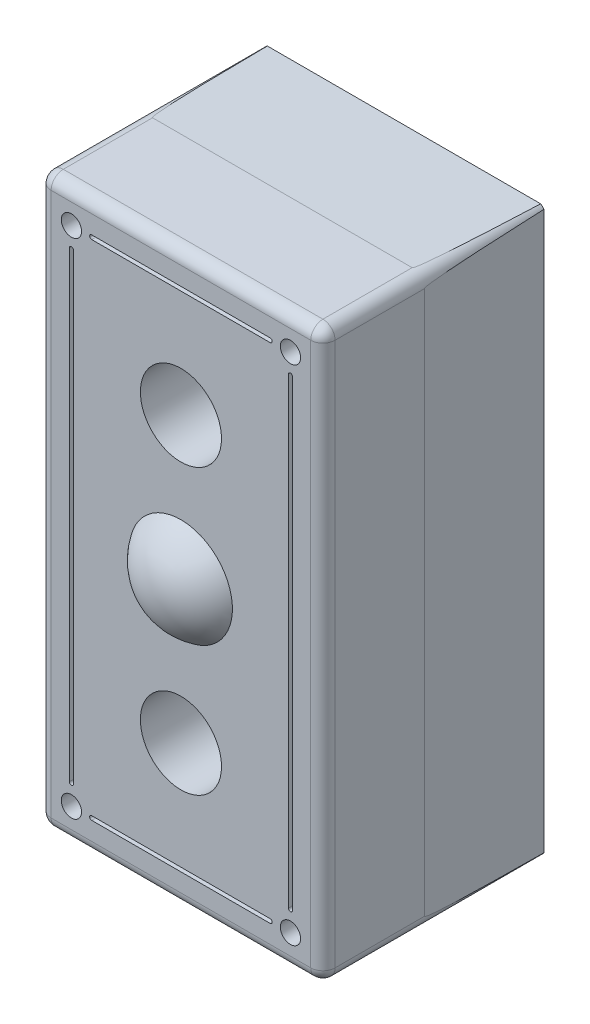
SolidWorks part; units mm, degrees
ref_plane "Front Plane" through (0, 0, 0) normal (0, 0, 1) x (1, 0, 0)
ref_plane "Top Plane" through (0, 0, 0) normal (0, 1, 0) x (1, 0, 0)
ref_plane "Right Plane" through (0, 0, 0) normal (1, 0, 0) x (0, 0, -1)
sketch "Sketch1" plane through (0, 0, 0) normal (0, 0, 1) x (1, 0, 0)
  line L1 (-35, 70) -> (35, 70)
  line L2 (-35, 70) -> (-35, -70)
  line L3 (-35, -70) -> (35, -70)
  line L4 (35, 70) -> (35, -70)
  line L5 (-35, 70) -> (35, -70) construction
  line L6 (-35, -70) -> (35, 70) construction
  point P0 (0, 0)
  dimension "D1" = 70
  dimension "D2" = 140
extrude "Boss-Extrude1" add sketch "Sketch1" against normal blind 30 draft 1
sketch "Sketch2" plane through (0, 0, 0) normal (0, 0, 1) x (1, 0, 0)
  line L4 (35, -70) -> (35, 70)
  line L5 (35, 70) -> (-35, 70)
  line L6 (-35, 70) -> (-35, -70)
  line L7 (-35, -70) -> (35, -70)
  line L8 (35, -70) -> (35, 70)
  line L9 (35, 70) -> (-35, 70)
  line L10 (-35, 70) -> (-35, -70)
  line L11 (-35, -70) -> (35, -70)
  dimension "D1" = 0
extrude "Boss-Extrude2" add sketch "Sketch2" along normal blind 25
sketch "Sketch3" plane through (0, 0, 25) normal (0, 0, 1) x (1, 0, 0)
  line L0 (35, -70) -> (35, 70) construction
  line L1 (35, 70) -> (-35, 70) construction
  circle A0 centre (27, 62) radius 2.5
  dimension "D1" = 8
  dimension "D3" = 5
  dimension "D2" = 8
extrude "Cut-Extrude1" cut sketch "Sketch3" against normal blind 25
mirror "Mirror1" about plane through (0, 0, 0) normal (1, 0, 0) of "Cut-Extrude1"
mirror "Mirror2" about plane through (0, 0, 0) normal (0, 1, 0) of "Mirror1", "Cut-Extrude1"
sketch "Sketch4" plane through (0, 0, 25) normal (0, 0, 1) x (1, 0, 0)
  line L0 (-35, -70) -> (35, -70) construction
  line L1 (35, 70) -> (-35, 70) construction
  circle A0 centre (0, -35) radius 10
  circle A1 centre (0, 35) radius 10
  point P4 (0, 0)
  point P6 (0, 0)
  dimension "D1" = 35
  dimension "D2" = 35
  dimension "D3" = 20
extrude "Cut-Extrude2" cut sketch "Sketch4" against normal blind 25
sketch "Sketch5" plane through (0, 0, 0) normal (0, 1, 0) x (1, 0, 0)
  line L0 (35, -25) -> (-35, -25) construction
  line L1 (0, -25) -> (0, -32) construction
  line L2 (0, -25) -> (0, -32)
  line L3 (12.6886, -25) -> (0, -25)
  arc A0 (12.6886, -25) -> (0, -32) centre (0, -17) cw
  dimension "D1" = 15
  dimension "D2" = 8
revolve "Revolve2" add sketch "Sketch5" angle 360 about L1
fillet "Fillet1" radius 3 8 edges at (-35, 0, 25) (35, 0, 25) (0, -70, 25) (0, 70, 25) (-35, -70, 12.5) (35, -70, 12.5) (-35, 70, 12.5) (35, 70, 12.5)
sketch "Sketch6" plane through (0, 0, 25) normal (0, 0, 1) x (1, 0, 0)
  line L0 (-22, 62) -> (22, 62) construction
  line L1 (-22, 62.5) -> (22, 62.5)
  line L2 (-22, 61.5) -> (22, 61.5)
  line L3 (-32, 70) -> (32, 70) construction
  line L4 (0, 0) -> (24.2245, 0) construction
  line L5 (-22, -62) -> (22, -62) construction
  line L6 (-22, -62.5) -> (22, -62.5)
  line L7 (-22, -61.5) -> (22, -61.5)
  line L8 (27, 57) -> (27, -57) construction
  line L9 (27.5, 57) -> (27.5, -57)
  line L10 (26.5, 57) -> (26.5, -57)
  line L11 (35, 67) -> (35, -67) construction
  line L12 (0, 0) -> (0, 18.2615) construction
  line L13 (-27, 57) -> (-27, -57) construction
  line L14 (-27.5, 57) -> (-27.5, -57)
  line L15 (-26.5, 57) -> (-26.5, -57)
  arc A0 (-22, 62.5) -> (-22, 61.5) centre (-22, 62) ccw
  arc A1 (22, 61.5) -> (22, 62.5) centre (22, 62) ccw
  circle A2 centre (27, 62) radius 2.5 construction
  circle A3 centre (-27, 62) radius 2.5 construction
  arc A4 (-22, -62.5) -> (-22, -61.5) centre (-22, -62) cw
  arc A5 (22, -61.5) -> (22, -62.5) centre (22, -62) cw
  arc A6 (27.5, 57) -> (26.5, 57) centre (27, 57) ccw
  arc A7 (26.5, -57) -> (27.5, -57) centre (27, -57) ccw
  circle A8 centre (27, -62) radius 2.5 construction
  circle A9 centre (27, 62) radius 2.5 construction
  arc A10 (-27.5, 57) -> (-26.5, 57) centre (-27, 57) cw
  arc A11 (-26.5, -57) -> (-27.5, -57) centre (-27, -57) cw
  point P2 (0, 62)
  point P18 (0, -62)
  point P25 (27, 0)
  point P39 (-27, 0)
  dimension "D3" = 5
  dimension "D4" = 5
  dimension "D6" = 5
  dimension "D8" = 5
  dimension "D1" = 1
  dimension "D2" = 8
  dimension "D5" = 1
  dimension "D7" = 8
extrude "Cut-Extrude3" cut sketch "Sketch6" against normal blind 1
